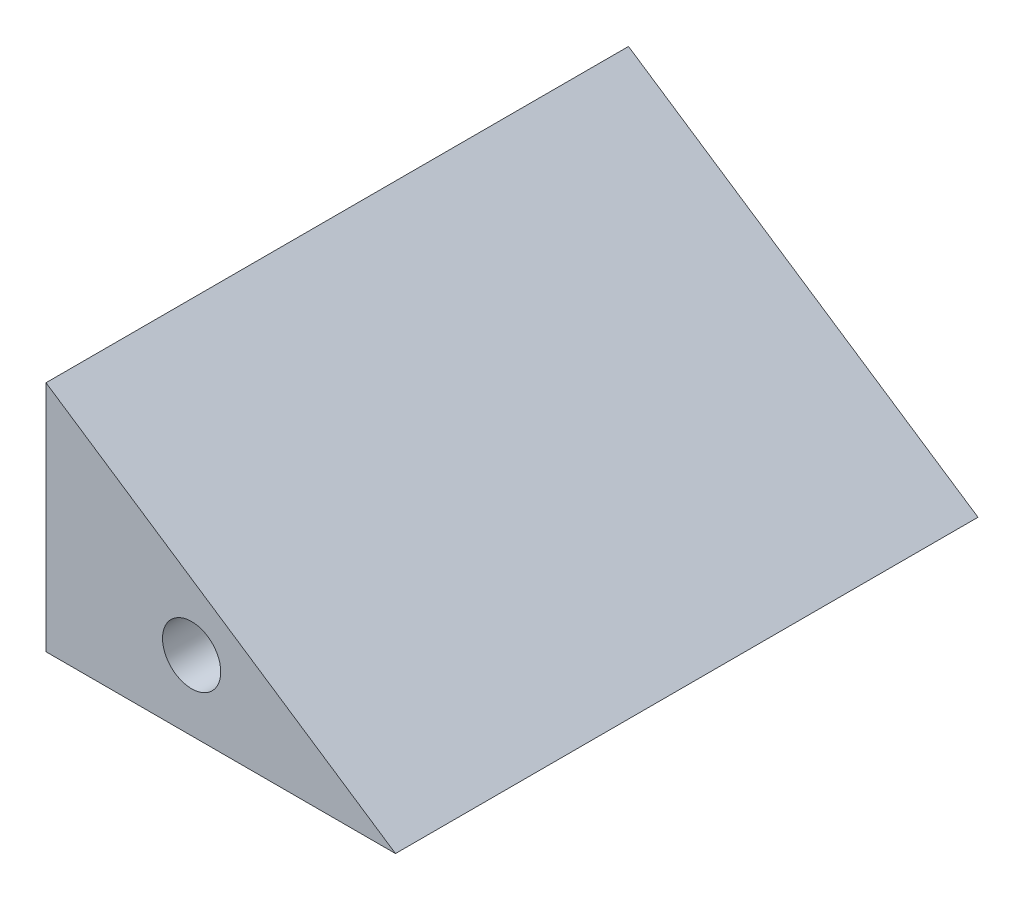
SolidWorks part; units mm, degrees
ref_plane "Спереди" through (0, 0, 0) normal (0, 0, 1) x (1, 0, 0)
ref_plane "Сверху" through (0, 0, 0) normal (0, 1, 0) x (1, 0, 0)
ref_plane "Справа" through (0, 0, 0) normal (1, 0, 0) x (0, 0, -1)
sketch "Эскиз1" plane through (0, 0, 0) normal (0, 0, 1) x (1, 0, 0)
  line L0 (0, 0) -> (0, 40)
  line L1 (0, 40) -> (60, 0)
  line L2 (60, 0) -> (0, 0)
  circle A0 centre (25, 12) radius 5
  dimension "D3" = 10
  dimension "D1" = 40
  dimension "D2" = 60
  dimension "D4" = 12
  dimension "D5" = 25
extrude "Кререж каретки боковой панели" add sketch "Эскиз1" along normal blind 100
